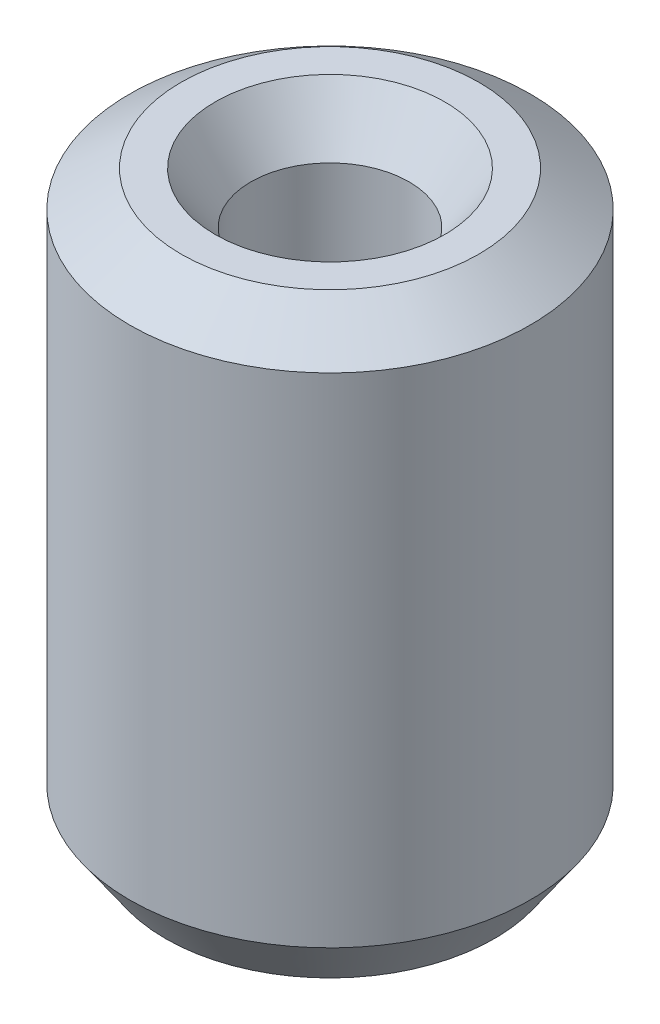
SolidWorks part; units mm, degrees
ref_plane "Front Plane" through (0, 0, 0) normal (0, 0, 1) x (1, 0, 0)
ref_plane "Top Plane" through (0, 0, 0) normal (0, 1, 0) x (1, 0, 0)
ref_plane "Right Plane" through (0, 0, 0) normal (1, 0, 0) x (0, 0, -1)
sketch "Sketch1" plane through (0, 0, 0) normal (0, 1, 0) x (1, 0, 0)
  circle A0 centre (0, 0) radius 10
  dimension "SLEEVE_OD" = 20
extrude "Boss-Extrude1" add sketch "Sketch1" along normal blind 29.2128
sketch "Sketch2" plane through (0, 0, 0) normal (0, 1, 0) x (1, 0, 0)
  circle A0 centre (0, 0) radius 3.9512
  dimension "BORE_D" = 7.9024
extrude "Cut-Extrude1" cut sketch "Sketch2" along normal through all
chamfer "Chamfer1" distance 1.7855 angle 55.156 4 edges at (0, 29.2128, 3.9512) (0, 0, 3.9512) (0, 0, 10) (0, 29.2128, 10) first distance on face at (0, 29.2128, 3.9512) first distance on face at (0, 0, 3.9512) first distance on face at (0, 29.2128, 10)
